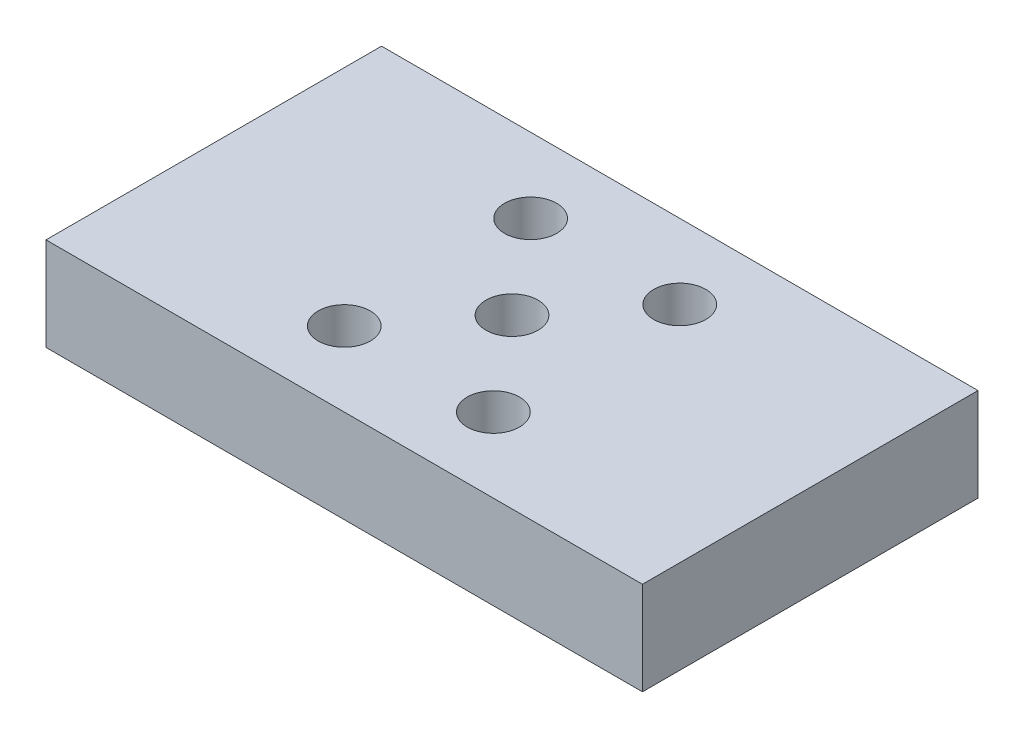
SolidWorks part; units mm, degrees
ref_plane "Front Plane" through (0, 0, 0) normal (0, 0, 1) x (1, 0, 0)
ref_plane "Top Plane" through (0, 0, 0) normal (0, 1, 0) x (1, 0, 0)
ref_plane "Right Plane" through (0, 0, 0) normal (1, 0, 0) x (0, 0, -1)
sketch "Sketch1" plane through (0, 0, 0) normal (0, 1, 0) x (1, 0, 0)
  line L0 (12, 4) -> (20, 4) construction
  line L1 (0, 0) -> (32, 0)
  line L2 (0, 0) -> (0, 18)
  line L3 (0, 18) -> (32, 18)
  line L4 (32, 0) -> (32, 18)
  line L5 (12, 14) -> (20, 14) construction
  line L6 (12, 14) -> (12, 4) construction
  circle A0 centre (12, 4) radius 1.4
  circle A1 centre (20, 4) radius 1.4
  circle A2 centre (20, 14) radius 1.4
  circle A3 centre (12, 14) radius 1.4
  circle A4 centre (16, 9) radius 1.4
  point P5 (16, 4)
  point P7 (16, 14)
  point P8 (16, 18)
  point P9 (16, 0)
  point P22 (12, 9)
  dimension "D3" = 2.8
  dimension "D9" = 2.8
  dimension "D1" = 18
  dimension "D2" = 32
  dimension "D6" = 8
  dimension "D7" = 4
  dimension "D8" = 10
  dimension "D4" = 2
  dimension "D5" = 2
extrude "Boss-Extrude1" add sketch "Sketch1" along normal blind 5
